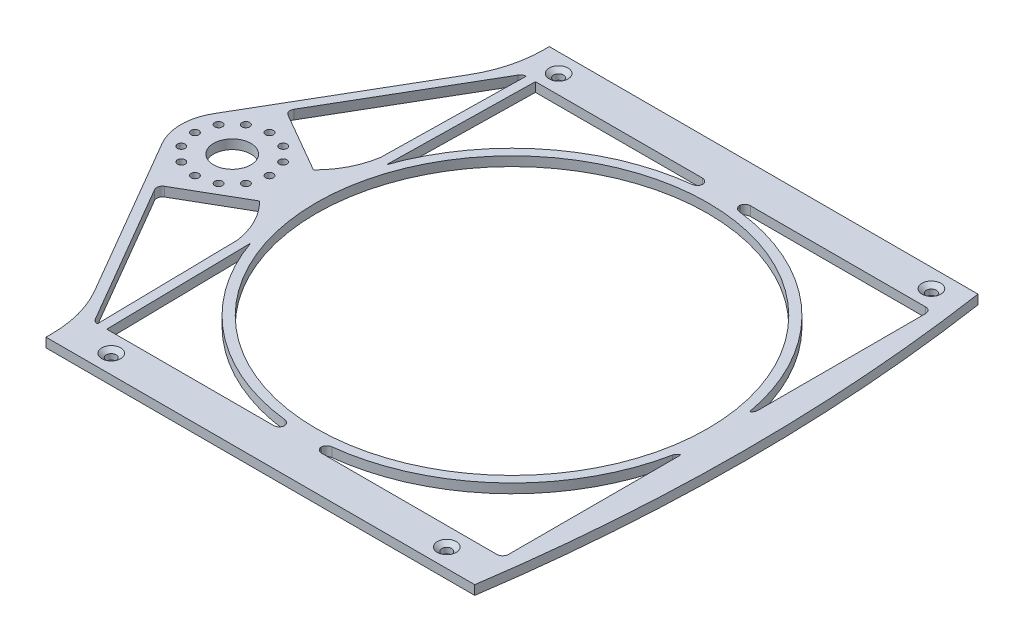
SolidWorks part; units mm, degrees
material "6061-T6 (SS)"
ref_plane "Front Plane" through (0, 0, 0) normal (0, 0, 1) x (1, 0, 0)
ref_plane "Top Plane" through (0, 0, 0) normal (0, 1, 0) x (1, 0, 0)
ref_plane "Right Plane" through (0, 0, 0) normal (1, 0, 0) x (0, 0, -1)
sketch "Sketch1" plane through (0, 0, 0) normal (0, 1, 0) x (1, 0, 0)
  line L0 (0, 0) -> (0, 133.35) construction
  line L1 (0, 133.35) -> (0, 171.45) construction
  line L2 (0, 171.45) -> (146.05, 171.45)
  line L3 (133.35, 0) -> (146.05, 0) construction
  line L4 (146.05, 0) -> (146.05, 171.45)
  line L5 (0, 146.05) -> (74.5442, 146.05) construction
  line L6 (0, 171.45) -> (-146.05, 171.45)
  line L7 (-146.05, 171.45) -> (-146.05, 0) construction
  line L8 (133.35, 0) -> (-146.05, 0) construction
  line L9 (-146.05, 0) -> (-146.05, -171.45) construction
  line L10 (-146.05, -171.45) -> (146.05, -171.45)
  line L11 (146.05, -171.45) -> (146.05, 0)
  line L12 (0, -133.35) -> (0, -171.45) construction
  line L13 (0, 0) -> (-190.6245, 0) construction
  line L14 (-190.6245, 0) -> (-190.6245, 25.4) construction
  line L17 (-220.8112, -17.5646) -> (-146.05, -146.05)
  line L18 (-146.05, -171.45) -> (-146.05, -146.05)
  line L19 (-220.8112, 17.5646) -> (-146.05, 146.05)
  line L20 (-146.05, 146.05) -> (-146.05, 171.45)
  circle A0 centre (0, 0) radius 133.35
  circle A2 centre (-190.6245, 0) radius 12.7
  circle A3 centre (-190.6245, 25.4) radius 2.6289
  circle A4 centre (-177.9245, 21.997) radius 2.6289
  circle A5 centre (-168.6274, 12.7) radius 2.6289
  circle A6 centre (-165.2245, 0) radius 2.6289
  circle A7 centre (-168.6274, -12.7) radius 2.6289
  circle A8 centre (-177.9245, -21.997) radius 2.6289
  circle A9 centre (-190.6245, -25.4) radius 2.6289
  circle A10 centre (-203.3245, -21.997) radius 2.6289
  circle A11 centre (-212.6215, -12.7) radius 2.6289
  circle A12 centre (-216.0245, 0) radius 2.6289
  circle A13 centre (-212.6215, 12.7) radius 2.6289
  circle A14 centre (-203.3245, 21.997) radius 2.6289
  arc A15 (-220.8112, -17.5646) -> (-220.8112, 17.5646) centre (-190.6245, 0) cw
  point P8 (-133.35, 0)
  point P45 (-190.6245, 0)
  dimension "D1" = 266.7
  dimension "D2" = 12.7
  dimension "D8" = 25.4
  dimension "D9" = 5.2578
  dimension "D12" = 34.925
  dimension "D3" = 38.1
  dimension "D4" = 25.4
  dimension "D5" = 12.7
  dimension "D6" = 38.1
  dimension "D7" = 190.6245
  dimension "D10" = 25.4
  dimension "D13" = 25.4
  dimension "D14" = 25.4
  dimension "D11" = 12
extrude "Extrude & center hole" add sketch "Sketch1" along normal blind 6.35
hole_wizard "CSK for 1/4 Flat Head Machine Screw (100)1" positions "Sketch4" profile "Sketch5" countersink size "1/4" standard "ANSI Inch" end condition through all
sketch "Sketch4" plane through (0, 6.35, 0) normal (0, 1, 0) x (1, 0, 0)
  line L0 (-146.05, -171.45) -> (146.05, -171.45) construction
  line L2 (146.05, -171.45) -> (146.05, 171.45) construction
  line L3 (146.05, 171.45) -> (-146.05, 171.45) construction
  line L4 (-146.05, 171.45) -> (-146.05, 146.05) construction
  line L5 (-146.05, -146.05) -> (-146.05, -171.45) construction
  point P0 (-114.3, -158.75)
  point P2 (114.3, -158.75)
  point P4 (127, 158.75)
  point P6 (-127, 158.75)
  dimension "D1" = 12.7
  dimension "D2" = 31.75
  dimension "D3" = 31.75
  dimension "D4" = 12.7
  dimension "D5" = 12.7
  dimension "D6" = 19.05
  dimension "D7" = 12.7
  dimension "D8" = 19.05
sketch "Sketch5" plane through (-114.3, 6.35, 158.75) normal (1, 0, 0) x (0, 0, 1)
  line L0 (0, 0) -> (0, 6.35)
  line L1 (0, 6.35) -> (3.3782, 6.35)
  line L2 (3.3782, 6.35) -> (3.3782, 2.5682)
  line L3 (3.3782, 2.5682) -> (6.4389, 0)
  line L5 (6.4389, 0) -> (0, 0)
  line L6 (-3.3782, 2.5682) -> (-6.4389, 0) construction
  line L11 (0, -6.35) -> (0, 107.95) construction
  dimension "Thru Hole Dia." = 6.7564
  dimension "Thru Hole Depth" = 6.35
  dimension "Near C'Sink Dia." = 12.8778
  dimension "Near C'Sink Angle" = 100
fillet "Fillet1" radius 79.7965 2 edges at (-146.05, 3.175, 146.05) (-146.05, 3.175, -146.05)
sketch "Sketch6" plane through (0, 6.35, 0) normal (0, 1, 0) x (1, 0, 0)
  line L0 (-139.3355, 10.0856) -> (-198.0812, 44.0025)
  line L1 (-198.0812, 44.0025) -> (-138.7033, 146.05)
  line L2 (-156.8759, 127.4444) -> (-220.8112, 17.5646) construction
  line L3 (-138.7033, 146.05) -> (-12.7777, 146.05)
  line L4 (0, 0) -> (-12.1757, 139.1684) construction
  line L5 (-12.1757, 139.1684) -> (-12.7777, 146.05)
  line L6 (0, 0) -> (0, 34.3566) construction
  line L7 (-190.6245, 0) -> (-173.435, 29.773) construction
  line L8 (-176.61, 24.2737) -> (-183.1786, 28.0661) construction
  line L9 (0, 0) -> (-97.1768, 0) construction
  line L10 (-198.0812, -44.0025) -> (-138.7033, -146.05)
  line L11 (-139.3355, -10.0856) -> (-198.0812, -44.0025)
  line L12 (-12.1757, -139.1684) -> (-12.7777, -146.05)
  line L13 (-138.7033, -146.05) -> (-12.7777, -146.05)
  line L14 (0, 0) -> (12.1757, 139.1684) construction
  line L15 (139.7, 24.6329) -> (139.7, 146.05)
  line L16 (146.05, -171.45) -> (146.05, 171.45) construction
  line L17 (0, 0) -> (137.5776, 24.2587) construction
  line L18 (137.5776, 24.2587) -> (139.7, 24.6329)
  line L19 (-12.7777, 146.05) -> (139.7, 146.05) construction
  line L20 (139.7, 146.05) -> (12.7777, 146.05)
  line L21 (12.1757, 139.1684) -> (12.7777, 146.05)
  line L22 (137.5776, -24.2587) -> (139.7, -24.6329)
  line L23 (139.7, -24.6329) -> (139.7, -146.05)
  line L24 (139.7, -146.05) -> (12.7777, -146.05)
  line L25 (12.1757, -139.1684) -> (12.7777, -146.05)
  arc A0 (-139.3355, 10.0856) -> (-12.1757, 139.1684) centre (0, 0) cw
  circle A1 centre (0, 0) radius 133.35 construction
  circle A2 centre (-127, 158.75) radius 6.4389 construction
  arc A3 (12.1757, -139.1684) -> (137.5776, -24.2587) centre (0, 0) ccw
  circle A5 centre (-177.9245, 21.997) radius 2.6289 construction
  arc A6 (-139.3355, -10.0856) -> (-12.1757, -139.1684) centre (0, 0) ccw
  arc A7 (12.1757, 139.1684) -> (137.5776, 24.2587) centre (0, 0) cw
  point P22 (-177.9245, 21.997)
  point P41 (0, 0)
  dimension "D1" = 6.35
  dimension "D7" = 6.35
  dimension "D2" = 6.35
  dimension "D3" = 12.7
  dimension "D4" = 5
  dimension "D5" = 6.35
  dimension "D6" = 5
  dimension "D8" = 6.35
  dimension "D9" = 170
extrude "Slotting" cut sketch "Sketch6" against normal through all
fillet "Fillet5" radius 3.9688 4 edges at (12.7777, 3.175, 146.05) (139.7, 3.175, 146.05) (137.5776, 3.175, 24.2587) (12.1757, 3.175, 139.1684)
fillet "Fillet6" radius 3.9688 4 edges at (139.7, 3.175, -24.6329) (139.7, 3.175, -146.05) (12.1757, 3.175, -139.1684) (12.7777, 3.175, -146.05)
fillet "Fillet7" radius 3.9688 5 edges at (-139.3355, 3.175, -10.0856) (-198.0812, 3.175, -44.0025) (-138.7033, 3.175, -146.05) (-12.1757, 3.175, -139.1684) (-12.7777, 3.175, -146.05)
fillet "Fillet8" radius 3.9688 5 edges at (-138.7033, 3.175, 146.05) (-12.7777, 3.175, 146.05) (-12.1757, 3.175, 139.1684) (-139.3355, 3.175, 10.0856) (-198.0812, 3.175, 44.0025)
sketch "Sketch7" plane through (0, 6.35, 0) normal (0, 1, 0) x (1, 0, 0)
  line L0 (-138.6754, 16.8888) -> (-136.4208, 146.05)
  line L1 (-131.8114, 46.2802) -> (-130.0699, 146.05)
  line L2 (-16.4144, 146.05) -> (-136.4208, 146.05) construction
  line L3 (-136.4208, 146.05) -> (-130.0699, 146.05)
  line L4 (0, 0) -> (-133.35, 0) construction
  line L5 (-138.6754, -16.8888) -> (-136.4208, -146.05)
  line L6 (-136.4208, -146.05) -> (-130.0699, -146.05)
  line L7 (-131.8114, -46.2802) -> (-130.0699, -146.05)
  arc A0 (-16.0154, 138.7789) -> (-138.7628, 16.1548) centre (0, 0) ccw construction
  arc A1 (-131.8114, 46.2802) -> (-138.6754, 16.8888) centre (0, 0) ccw
  circle A2 centre (0, 0) radius 133.35 construction
  arc A3 (-131.8114, -46.2802) -> (-138.6754, -16.8888) centre (0, 0) cw
  dimension "D1" = 6.35
  dimension "D2" = 91
extrude "Motor side supports" add sketch "Sketch7" against normal up to surface (6.35 mm away) up to face at (-112.8817, 0, 95.162)
sketch "Sketch9" plane through (0, 6.35, 0) normal (0, 1, 0) x (1, 0, 0)
  line L0 (146.05, 0) -> (158.75, 0) construction
  line L1 (146.05, -171.45) -> (146.05, 171.45) construction
  line L2 (146.05, 171.45) -> (146.05, -171.45)
  arc A0 (146.05, 171.45) -> (146.05, -171.45) centre (-1004.8875, 0) cw
  dimension "D1" = 12.7
extrude "Opposite motor side thickening" add sketch "Sketch9" against normal up to surface (6.35 mm away) up to face at (-155.6713, 0, 60.6233)
sketch "Sketch10" plane through (0, 6.35, 0) normal (0, 1, 0) x (1, 0, 0)
  line L0 (-194.6325, 42.0114) -> (-144.6893, 13.1767) construction
  line L1 (-136.4208, 146.05) -> (-138.6754, 16.8888) construction
  line L4 (-133.35, 0) -> (-177.9245, 0) construction
  line L7 (-138.1227, 48.5516) -> (-138.6754, 16.8888)
  line L8 (-153.6095, 18.3267) -> (-144.6893, 13.1767)
  line L9 (-153.6095, -18.3267) -> (-144.6893, -13.1767)
  line L10 (-138.1227, -48.5516) -> (-138.6754, -16.8888)
  circle A3 centre (0, 0) radius 133.35 construction
  circle A4 centre (-190.6245, 0) radius 12.7 construction
  arc A7 (-153.6095, 18.3267) -> (-138.1227, 48.5516) centre (-191.9464, 57.0501) ccw
  arc A8 (-144.6893, 13.1767) -> (-138.7628, 16.1548) centre (-142.7049, 16.6137) ccw construction
  arc A9 (-138.6754, 16.8888) -> (-138.7628, 16.1548) centre (0, 0) ccw construction
  arc A10 (-144.6893, 13.1767) -> (-138.7628, 16.1548) centre (-142.7049, 16.6137) ccw
  arc A11 (-138.6754, 16.8888) -> (-138.7628, 16.1548) centre (0, 0) ccw
  arc A12 (-138.6754, -16.8888) -> (-138.7628, -16.1548) centre (0, 0) cw
  arc A13 (-144.6893, -13.1767) -> (-138.7628, -16.1548) centre (-142.7049, -16.6137) cw
  arc A14 (-153.6095, -18.3267) -> (-138.1227, -48.5516) centre (-191.9464, -57.0501) cw
  point P8 (0, 0)
extrude "Motor side thickening" add sketch "Sketch10" against normal up to surface (6.35 mm away) up to face at (-155.6713, 0, 60.6233)
